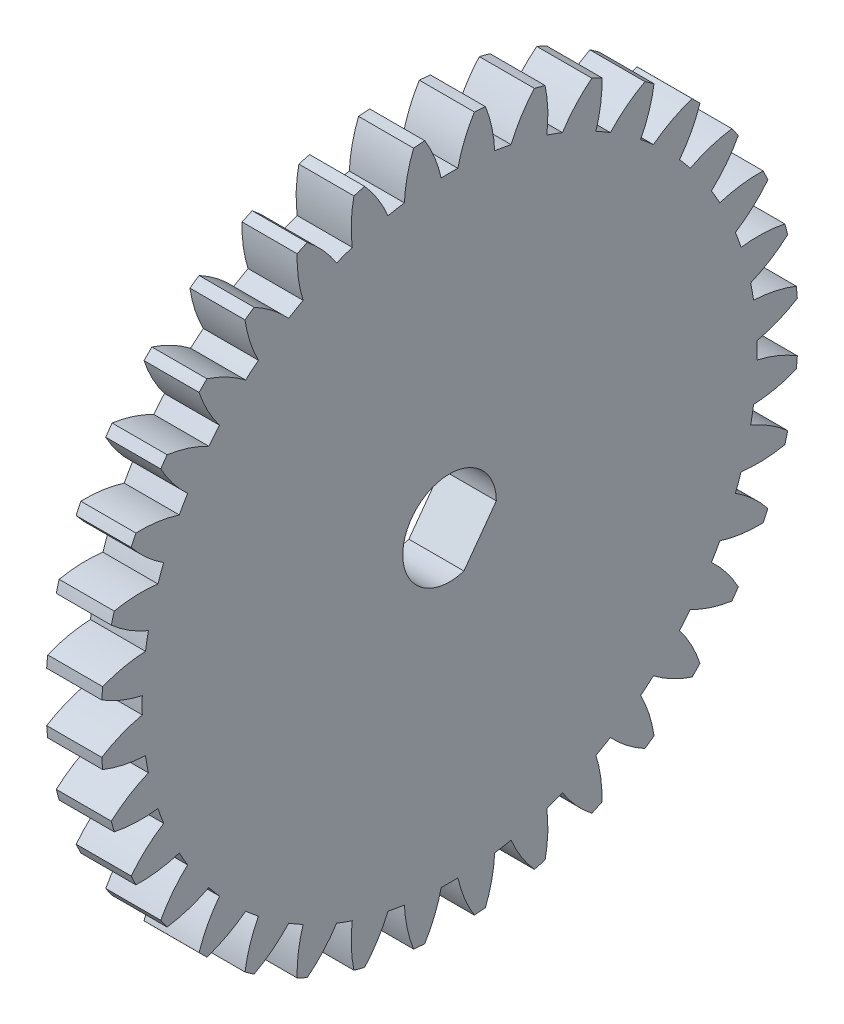
SolidWorks part; units mm, degrees
ref_plane "Plane1" through (0, 0, 0) normal (0, 0, 1) x (1, 0, 0)
ref_plane "Plane2" through (0, 0, 0) normal (0, 1, 0) x (1, 0, 0)
ref_plane "Plane3" through (0, 0, 0) normal (1, 0, 0) x (0, 0, -1)
sketch "HoldingSke" plane through (0, 0, 0) normal (0, 1, 0) x (1, 0, 0)
  line L0 (0, 0) -> (0.809, -0.5878)
  line L1 (-15, 0) -> (100, 0) construction
  line L2 (0, 0) -> (-2.1039, 2.3779)
  line L3 (0, 0) -> (-11.863, 4.5341)
  line L4 (0, 0) -> (6.9867, 5.0761)
  line L5 (0, 0) -> (-46.8476, -17.4728)
  line L6 (0, 0) -> (-2.4869, -1.6779)
  line L7 (-2.1039, 2.3779) -> (8.6586, 51.2059)
  line L8 (-76.2, 54.61) -> (-76.1, 54.61)
  line L9 (-71.009, 38.7566) -> (-53.1078, 45.2721)
  line L10 (-76.2, 71.12) -> (104.1128, 71.12)
  line L11 (0, 0) -> (-3, 0)
  line L12 (-76.2, 101.6) -> (-76.162, 101.6)
  line L13 (24.9733, 27.94) -> (52.9518, 28.4284)
  line L14 (24.9733, 27.94) -> (24.9743, 27.94)
  line L15 (24.9733, 27.94) -> (100.4006, 29.5858)
  line L16 (-63.627, -1) -> (-12.827, -1)
  circle A0 centre (0, 0) radius 0.4
  circle A1 centre (0, 0) radius 16.749
  circle A2 centre (0, 0) radius 37.5
  circle A3 centre (0, 0) radius 0.4
  dimension "Num_teeth" = 36
  dimension "Pitch_radius" = 180.3128
  dimension "Width" = 3
  dimension "Thickness" = 3
sketch "BasProSke" plane through (0, 0, 0) normal (0, 1, 0) x (1, 0, 0)
  line L0 (-10, 0) -> (60, 0) construction
  line L1 (0, 0) -> (0, 19)
  line L2 (0, 0) -> (3, 0)
  line L3 (3, 0) -> (3, 19)
  line L4 (3, 19) -> (0, 19)
  dimension "Thickness" = 3
  dimension "Diameter" = 38
revolve "Base-Revolve" add sketch "BasProSke" angle 360 about L0
sketch "TooCutSke" plane through (0, 0, 0) normal (1, 0, 0) x (0, 0, -1)
  line L1 (0, 0) -> (0, 107) construction
  line L2 (0, 0) -> (-0.8516, 17.9798) construction
  line L3 (0, 0) -> (-3.1351, 35.8344) construction
  line L4 (-0.8516, 17.9798) -> (-1.5676, 17.9172) construction
  arc A0 (0.4547, 16.7428) -> (-0.4547, 16.7428) centre (0, 0) ccw
  arc A1 (1.3689, 18.9761) -> (-1.3689, 18.9761) centre (0, 0) ccw
  circle A2 centre (0, 0) radius 18 construction
  circle A3 centre (0, 0) radius 16.9145 construction
  arc A4 (-0.4547, 16.7428) -> (-1.3689, 18.9761) centre (-7.4808, 15.1702) ccw
  arc A5 (1.3689, 18.9761) -> (0.4547, 16.7428) centre (7.4808, 15.1702) ccw
extrude "ToothCut" cut sketch "TooCutSke" along normal through all
fillet "Breaks" [suppressed] radius 0.02 tangent propagation no
fillet "RootFillets" [suppressed] radius 0.251
pattern_circular "TeethCuts" count 36 every 10 about axis through (-10, 0, 0) along (1, 0, 0) of "ToothCut", "RootFillets", "Breaks"
sketch "HubNeaOneSke" plane through (0, 0, 0) normal (-1, 0, 0) x (0, 0, 1)
  circle A0 centre (0, 0) radius 16.749
  dimension "Diameter" = 33.498
extrude "HubNearOne" [suppressed] add sketch "HubNeaOneSke" along normal blind 47.0001
sketch "HubNeaBotSke" plane through (0, 0, 0) normal (-1, 0, 0) x (0, 0, 1)
  circle A0 centre (0, 0) radius 16.749
  dimension "Diameter" = 33.498
extrude "HubNearBoth" [suppressed] add sketch "HubNeaBotSke" along normal blind 23.5
ref_plane "FarPln" through (3, 0, 0) normal (1, 0, 0) x (0, 0, -1)
sketch "HubFarSke" plane through (3, 0, 0) normal (1, 0, 0) x (0, 0, -1)
  circle A0 centre (0, 0) radius 16.749
  dimension "Diameter" = 33.498
extrude "HubFar" [suppressed] add sketch "HubFarSke" along normal blind 23.5
sketch "BorSke" plane through (0, 0, 0) normal (1, 0, 0) x (0, 0, -1)
  circle A0 centre (0, 0) radius 0.4
  dimension "Diameter" = 0.8
extrude "Bore" cut sketch "BorSke" along normal mid plane 100.0001
sketch "KeySke" plane through (0, 0, 0) normal (1, 0, 0) x (0, 0, -1)
  line L0 (-0.05, 0) -> (-0.05, 0.5)
  line L1 (-0.05, 0.5) -> (0.05, 0.5)
  line L2 (0.05, 0.5) -> (0.05, 0)
  line L3 (0, 0) -> (0, 34) construction
  line L4 (-0.05, 0) -> (0.05, 0)
extrude "Keyway" [suppressed] cut sketch "KeySke" along normal mid plane 100.0001
pattern_circular "Keyway2" [suppressed] count 2 every 90 about axis through (-10, 0, 0) along (1, 0, 0) reverse direction yes
sketch "Sketch2" plane through (0, 0, 0) normal (-1, 0, 0) x (0, 0, 1)
  line L0 (-2.55, 0) -> (-0.7853, -2.4261)
  arc A0 (-0.7853, -2.4261) -> (-2.55, 0) centre (0, 0) ccw
extrude "Cut-Extrude2" cut sketch "Sketch2" against normal through all
equation "' \"Module@HoldingSke\" = 6.35"
equation "' \"Num_teeth@HoldingSke\" = 12"
equation "' \"Ap@HoldingSke\" =  20"
equation "' \"Ap@HoldingSke\" = 20"
equation "' \"Width@HoldingSke\" = 0.5 * 25.4"
equation "' \"Hub_dia@HoldingSke\"= 1 * 25.4"
equation "' \"Hub_dia@HoldingSke\" = 1 * 25.4"
equation "' \"Overall_len@HoldingSke\" = 1.0 * 25.4"
equation "' \"Bore@HoldingSke\" = 0.75 * 25.4"
equation "' \"T_dim@HoldingSke\" = 0.1 * 25.4"
equation "' \"Width@KeySke\" = 0.25 * 25.4"
equation "' \"Show_teeth@HoldingSke\" = 13"
equation "' \"Backlash@HoldingSke\" = 0.009 * 25.4"
equation "' \"Addendum_fac@HoldingSke\" = 1.0"
equation "' \"Dedendum_fac@HoldingSke\" = 1.25"
equation "' \"Dedendum_add@HoldingSke\" = 0.00005 * 25.4"
equation "' \"Clearance_fac@HoldingSke\" = 0.25"
equation "\"Pitch@HoldingSke\" = 1 / \"Module@HoldingSke\""
equation "\"Overcut_dia@TooCutSke\" = (\"Num_teeth@HoldingSke\" + 2 * \"Addendum_fac@HoldingSke\") / \"Pitch@HoldingSke\" + 0.002 * 25.4"
equation "\"Pitch_dia@TooCutSke\" = \"Num_teeth@HoldingSke\" / \"Pitch@HoldingSke\""
equation "\"Base_dia@TooCutSke\" = \"Num_teeth@HoldingSke\" / \"Pitch@HoldingSke\" * cos((\"Ap@HoldingSke\"  * 3.14159265 / 180))"
equation "\"Root_dia@TooCutSke\" = (\"Num_teeth@HoldingSke\" + 2) / \"Pitch@HoldingSke\" - 2 * (\"Addendum_fac@HoldingSke\" + \"Dedendum_fac@HoldingSke\") / \"Pitch@HoldingSke\" - \"Dedendum_add@HoldingSke\" * 2"
equation "\"Half_ang@TooCutSke\" = 180 / \"Num_teeth@HoldingSke\""
equation "\"Half_CT@TooCutSke\" = \"Num_teeth@HoldingSke\" / \"Pitch@HoldingSke\" * sin((3.14159265 / 2 / \"Num_teeth@HoldingSke\")) / 2 - 7 * \"Backlash@HoldingSke\" / 4"
equation "\"Flank_rad@TooCutSke\" = \"Num_teeth@HoldingSke\" / \"Pitch@HoldingSke\" / 5"
equation "\"Radius@RootFillets\" = \"Clearance_fac@HoldingSke\" / \"Pitch@HoldingSke\" + \"Dedendum_add@HoldingSke\""
equation "\"Break_rad@Breaks\" = 0.02 / \"Pitch@HoldingSke\""
equation "\"Thickness@HoldingSke\" = \"Width@HoldingSke\""
equation "\"OAL@HoldingSke\" = \"Thickness@HoldingSke\""
equation "\"MHD@HoldingSke\" = (\"Num_teeth@HoldingSke\" + 2) / \"Pitch@HoldingSke\" - 2 * (\"Addendum_fac@HoldingSke\" + \"Dedendum_fac@HoldingSke\")  / \"Pitch@HoldingSke\" - \"Dedendum_add@HoldingSke\" * 2"
equation "\"MBD@HoldingSke\" = (\"Num_teeth@HoldingSke\" + 2) / \"Pitch@HoldingSke\" - 2 * (\"Addendum_fac@HoldingSke\" + \"Dedendum_fac@HoldingSke\")  / \"Pitch@HoldingSke\" - \"Dedendum_add@HoldingSke\" * 2 - 0.002 * 25.4"
equation "\"MHD@HoldingSke\" = ((sgn( \"MHD@HoldingSke\" - \"Hub_dia@HoldingSke\" )-1)*( \"MHD@HoldingSke\" - \"Hub_dia@HoldingSke\" ))/-2+ \"Hub_dia@HoldingSke\""
equation "\"MBD@HoldingSke\" = ((sgn( \"MBD@HoldingSke\" - \"Bore@HoldingSke\" )-1)*( \"MBD@HoldingSke\" - \"Bore@HoldingSke\" ))/-2+ \"Bore@HoldingSke\""
equation "\"OAL@HoldingSke\" = ((sgn( \"OAL@HoldingSke\" - \"Overall_len@HoldingSke\" )+1)*( \"OAL@HoldingSke\" - \"Overall_len@HoldingSke\" ))/2 + \"Overall_len@HoldingSke\" + 0.000002 * 25.4"
equation "\"Num_teeth@TeethCuts\" = int( \"Show_teeth@HoldingSke\" ) + 1"
equation "\"Num_teeth@TeethCuts\" = ((sgn( \"Num_teeth@TeethCuts\" - \"Num_teeth@HoldingSke\" )-1)*( \"Num_teeth@TeethCuts\" - \"Num_teeth@HoldingSke\" ))/-2+ \"Num_teeth@HoldingSke\""
equation "\"Num_teeth@TeethCuts\" = ((sgn( \"Num_teeth@TeethCuts\" - 2.0)+1)*( \"Num_teeth@TeethCuts\" - 2.0))/2 +2.0"
equation "\"Angle@TeethCuts\" = 360.0 / \"Num_teeth@HoldingSke\""
equation "\"Diameter@BasProSke\" = (\"Num_teeth@HoldingSke\" + 2 * \"Addendum_fac@HoldingSke\") / \"Pitch@HoldingSke\""
equation "\"Thickness@BasProSke\"  = \"Thickness@HoldingSke\""
equation "' \"Fillet_rad@BasProSke\" =  \"Thickness@HoldingSke\" * 0.05"
equation "' \"Fillet_rad@BasProSke\" = \"Thickness@HoldingSke\" * 0.05"
equation "\"MHD@HoldingSke\" = ((sgn( \"MHD@HoldingSke\" - \"Root_dia@TooCutSke\" )-1)*( \"MHD@HoldingSke\" - \"Root_dia@TooCutSke\" ))/-2+ \"Root_dia@TooCutSke\""
equation "\"Diameter@HubNeaOneSke\" = \"MHD@HoldingSke\""
equation "\"Length@HubNearOne\" = \"OAL@HoldingSke\" - \"Thickness@BasProSke\""
equation "\"Diameter@HubNeaBotSke\" = \"MHD@HoldingSke\""
equation "\"Length@HubNearBoth\" = ( \"OAL@HoldingSke\" - \"Thickness@BasProSke\" ) / 2.0"
equation "\"Thickness@FarPln\" = \"Thickness@BasProSke\""
equation "\"Diameter@HubFarSke\" = \"MHD@HoldingSke\""
equation "\"Length@HubFar\" = ( \"OAL@HoldingSke\" - \"Thickness@BasProSke\" ) / 2.0"
equation "\"Diameter@BorSke\" = \"MBD@HoldingSke\""
equation "\"D1@Bore\" = \"OAL@HoldingSke\" * 2.0"
equation "\"D1@Keyway\" = \"OAL@HoldingSke\" * 2.0"
equation "\"Offset@KeySke\" = \"T_dim@HoldingSke\" + \"MBD@HoldingSke\" / 2.0"
